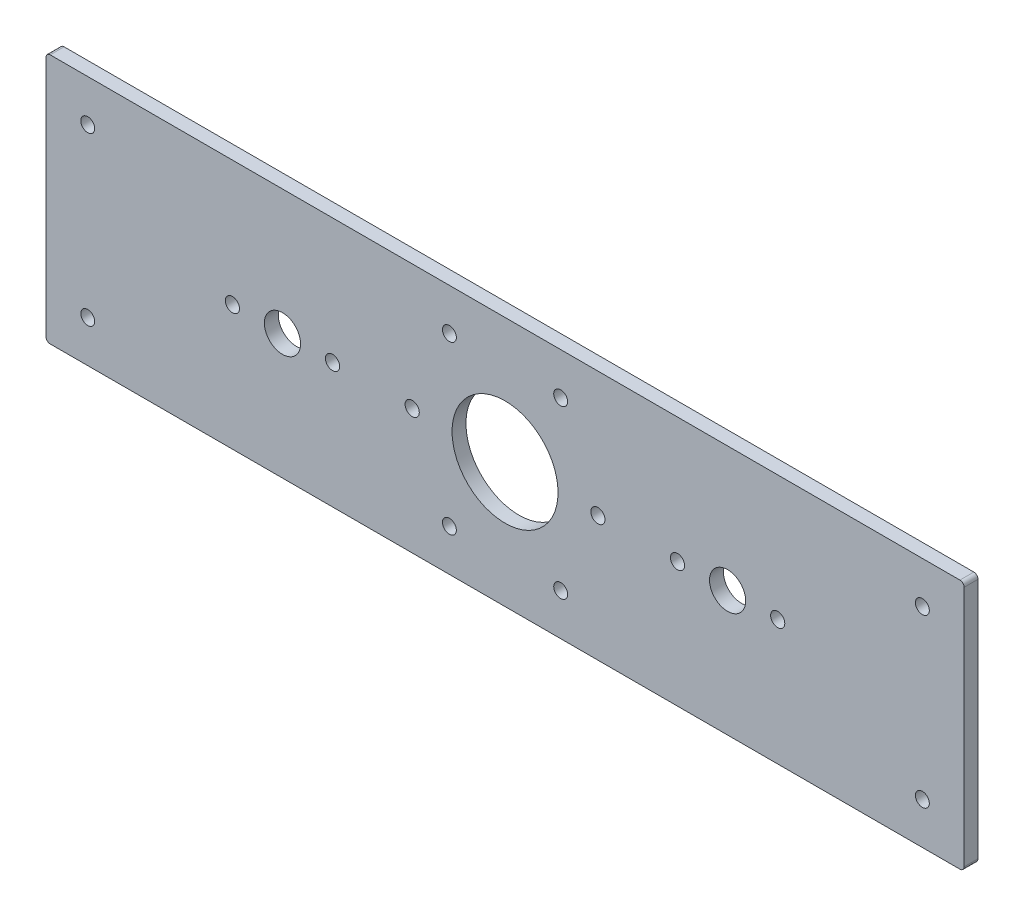
SolidWorks part; units mm, degrees
ref_plane "Front Plane" through (0, 0, 0) normal (0, 0, 1) x (1, 0, 0)
ref_plane "Top Plane" through (0, 0, 0) normal (0, 1, 0) x (1, 0, 0)
ref_plane "Right Plane" through (0, 0, 0) normal (1, 0, 0) x (0, 0, -1)
sketch "Sketch1" plane through (0, 0, 0) normal (0, 0, 1) x (1, 0, 0)
  line L0 (-165, 0) -> (165, 0) construction
  line L1 (165, -45) -> (-165, -45)
  line L2 (165, -45) -> (165, 45)
  line L3 (165, 45) -> (-165, 45)
  line L4 (-165, -45) -> (-165, 45)
  line L5 (165, -45) -> (-165, 45) construction
  line L6 (165, 45) -> (-165, -45) construction
  line L8 (0, -33.3754) -> (33.3754, 0) construction
  line L9 (0, -33.3754) -> (-33.3754, 0) construction
  line L10 (-33.3754, 0) -> (0, 33.3754) construction
  line L11 (33.3754, 0) -> (0, 33.3754) construction
  line L12 (0, -33.3754) -> (0, 33.3754) construction
  line L13 (-33.3754, 0) -> (33.3754, 0) construction
  circle A0 centre (0, 0) radius 19.05
  circle A1 centre (-33.3754, 0) radius 2.55
  circle A2 centre (33.3754, 0) radius 2.55
  point P0 (0, 0)
  dimension "D3" = 38.1
  dimension "D4" = 47.2
  dimension "D5" = 47.2
  dimension "D8" = 5.1
  dimension "D9" = 5.1
  dimension "D1" = 90
  dimension "D2" = 330
  dimension "D6" = 90
  dimension "D7" = 90
extrude "Boss-Extrude1" add sketch "Sketch1" along normal mid plane 5
sketch "Sketch2" plane through (0, 0, 2.5) normal (0, 0, 1) x (1, 0, 0)
  line L2 (-150, 45) -> (-150, -45)
  line L3 (-150, 45) -> (-150, -45) construction
  line L5 (150, -45) -> (150, 45)
  line L6 (150, -45) -> (150, 45) construction
  line L23 (165, 30) -> (-165, 30)
  line L24 (165, 30) -> (-165, 30) construction
  line L25 (0, 45) -> (0, -45) construction
  line L26 (-165, -30) -> (165, -30)
  line L27 (-165, -30) -> (165, -30) construction
  line L28 (165, 45) -> (-165, 45) construction
  line L29 (-165, -45) -> (165, -45) construction
  line L30 (-20, 45) -> (-20, -45) construction
  line L31 (20, 45) -> (20, -45) construction
  circle A0 centre (-150, 30) radius 2.5
  circle A1 centre (-150, -30) radius 2.5
  circle A2 centre (-20, 30) radius 2.5
  circle A3 centre (-20, -30) radius 2.5
  circle A4 centre (20, -30) radius 2.5
  circle A5 centre (20, 30) radius 2.5
  circle A6 centre (150, 30) radius 2.5
  circle A7 centre (150, -30) radius 2.5
  dimension "D7" = 5
  dimension "D8" = 5
  dimension "D9" = 5
  dimension "D10" = 5
  dimension "D11" = 5
  dimension "D12" = 5
  dimension "D13" = 5
  dimension "D14" = 5
  dimension "D1" = 15
  dimension "D2" = 15
  dimension "D3" = 15
  dimension "D4" = 15
  dimension "D5" = 20
  dimension "D6" = 20
extrude "Cut-Extrude1" cut sketch "Sketch2" against normal through all
sketch "Sketch3" plane through (0, 0, 2.5) normal (0, 0, 1) x (1, 0, 0)
  line L0 (0, 0) -> (-49.4534, 0) construction
  circle A0 centre (-62, 0) radius 2.55
  circle A1 centre (-98, 0) radius 2.55
  circle A2 centre (-80, 0) radius 6.5
  dimension "D1" = 5.1
  dimension "D2" = 5.1
  dimension "D3" = 13
  dimension "D4" = 80
  dimension "D5" = 18
  dimension "D6" = 18
extrude "Cut-Extrude2" cut sketch "Sketch3" against normal through all
mirror "Mirror1" about plane through (0, 0, 0) normal (1, 0, 0) of "Cut-Extrude2"
fillet "Fillet1" radius 1.5 4 edges at (-165, -45, 0) (165, -45, 0) (165, 45, 0) (-165, 45, 0)
equation "\"D4@Sketch3\"=160/2"
